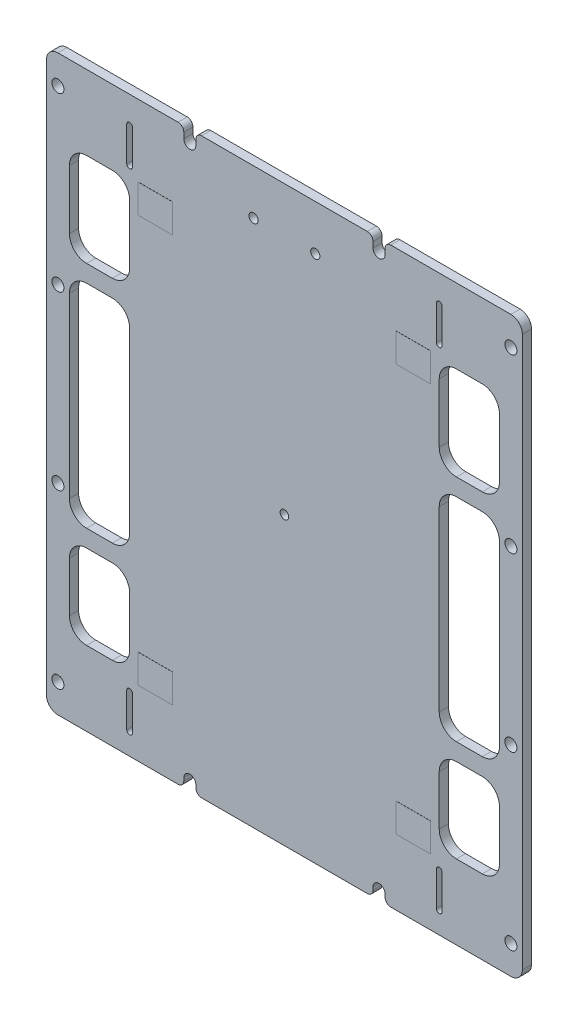
SolidWorks part; units mm, degrees
material "FR4_stuffedProtoboard"
ref_plane "Front Plane" through (0, 0, 0) normal (0, 0, 1) x (1, 0, 0)
ref_plane "Top Plane" through (0, 0, 0) normal (0, 1, 0) x (1, 0, 0)
ref_plane "Right Plane" through (0, 0, 0) normal (1, 0, 0) x (0, 0, -1)
sketch "Sketch1" plane through (0, 0, 0) normal (0, 0, 1) x (1, 0, 0)
  line L1 (-39.5, -50) -> (39.5, -50)
  line L2 (-41.5, -48) -> (-41.5, 48)
  line L3 (-39.5, 50) -> (39.5, 50)
  line L4 (41.5, -48) -> (41.5, 48)
  line L5 (-41.5, -50) -> (41.5, 50) construction
  line L6 (-41.5, 50) -> (41.5, -50) construction
  arc A0 (-39.5, -50) -> (-41.5, -48) centre (-39.5, -48) cw
  arc A1 (39.5, -50) -> (41.5, -48) centre (39.5, -48) ccw
  arc A2 (39.5, 50) -> (41.5, 48) centre (39.5, 48) cw
  arc A3 (-41.5, 48) -> (-39.5, 50) centre (-39.5, 48) cw
  point P0 (0, 0)
  dimension "D3" = 2
  dimension "D1" = 100
  dimension "D2" = 83
extrude "boardOutline" add sketch "Sketch1" along normal blind 1.6
sketch "Sketch2" plane through (0, 0, 1.6) normal (0, 0, 1) x (1, 0, 0)
  line L0 (39.5, 50) -> (-39.5, 50) construction
  line L1 (-41.5, 48) -> (-41.5, -48) construction
  line L2 (-5.385, 42.1) -> (5.385, 42.1) construction
  line L3 (-38, 44.2) -> (-38, 4.2) construction
  line L4 (0, 42.1) -> (0, 50) construction
  circle A0 centre (0, 0) radius 0.75
  circle A1 centre (-38, 44.2) radius 1.05 construction
  circle A2 centre (37.5, 44.2) radius 1.05 construction
  circle A3 centre (37.5, 4.2) radius 1.05 construction
  circle A4 centre (37.5, -35.8) radius 1.05 construction
  circle A5 centre (-38, 4.2) radius 1.05 construction
  circle A6 centre (-38, -35.8) radius 1.05 construction
  circle A7 centre (-5.385, 42.1) radius 0.8
  circle A8 centre (5.385, 42.1) radius 0.8
  dimension "D1" = 1.5
  dimension "D2" = 2.1
  dimension "D9" = 10.77
  dimension "D7" = 1.6
  dimension "D11" = 7.9
  dimension "D3" = 5.8
  dimension "D4" = 3.5
  dimension "D8" = 40
  dimension "D10" = 37.5
  dimension "D5" = 2
  dimension "D6" = 3
extrude "componentHoles" cut sketch "Sketch2" against normal through all
sketch "Sketch4" plane through (0, 0, 1.6) normal (0, 0, 1) x (1, 0, 0)
  line L0 (-27, 39.25) -> (-27, 45.25) construction
  line L1 (-27.5, 39.25) -> (-27.5, 45.25)
  line L2 (-26.5, 39.25) -> (-26.5, 45.25)
  line L3 (39.5, 50) -> (-39.5, 50) construction
  line L4 (-41.5, 48) -> (-41.5, -48) construction
  line L5 (27, 39.25) -> (27, 45.25) construction
  line L6 (26.5, 39.25) -> (26.5, 45.25)
  line L7 (27.5, 39.25) -> (27.5, 45.25)
  line L8 (27, -46.25) -> (27, -40.25) construction
  line L9 (26.5, -46.25) -> (26.5, -40.25)
  line L10 (27.5, -46.25) -> (27.5, -40.25)
  line L11 (-27, -46.25) -> (-27, -40.25) construction
  line L12 (-27.5, -46.25) -> (-27.5, -40.25)
  line L13 (-26.5, -46.25) -> (-26.5, -40.25)
  line L14 (-27, 39.25) -> (27, 39.25) construction
  line L15 (0, 39.25) -> (0, 50) construction
  arc A0 (-27.5, 39.25) -> (-26.5, 39.25) centre (-27, 39.25) ccw
  arc A1 (-26.5, 45.25) -> (-27.5, 45.25) centre (-27, 45.25) ccw
  arc A2 (26.5, 39.25) -> (27.5, 39.25) centre (27, 39.25) ccw
  arc A3 (27.5, 45.25) -> (26.5, 45.25) centre (27, 45.25) ccw
  arc A4 (26.5, -46.25) -> (27.5, -46.25) centre (27, -46.25) ccw
  arc A5 (27.5, -40.25) -> (26.5, -40.25) centre (27, -40.25) ccw
  arc A6 (-27.5, -46.25) -> (-26.5, -46.25) centre (-27, -46.25) ccw
  arc A7 (-26.5, -40.25) -> (-27.5, -40.25) centre (-27, -40.25) ccw
  point P2 (-27, 42.25)
  point P16 (27, 42.25)
  point P23 (27, -43.25)
  point P30 (-27, -43.25)
  dimension "D1" = 4.75
  dimension "D2" = 14
  dimension "D3" = 1
  dimension "D4" = 6
  dimension "D7" = 54
  dimension "D9" = 79.5
  dimension "D5" = 2
  dimension "D6" = 2
extrude "solarCellContactHoles" cut sketch "Sketch4" against normal blind 1.6
sketch "Sketch3" plane through (0, 0, 1.6) normal (0, 0, 1) x (1, 0, 0)
  line L1 (-34.5, 37) -> (-30, 37)
  line L2 (-37.5, 34) -> (-37.5, 23.7)
  line L3 (-34.5, 20.7) -> (-30, 20.7)
  line L4 (-27, 34) -> (-27, 23.7)
  line L5 (-41.5, 48) -> (-41.5, -48) construction
  line L6 (-30, -22.3) -> (-34.5, -22.3)
  line L9 (0, 50) -> (0, -50) construction
  line L10 (39.5, 50) -> (-39.5, 50) construction
  line L11 (-39.5, -50) -> (39.5, -50) construction
  line L12 (-27, -25.3) -> (-27, -34)
  line L13 (-30, -37) -> (-34.5, -37)
  line L14 (-37.5, -25.3) -> (-37.5, -34)
  line L19 (-30, -19.3) -> (-34.5, -19.3)
  line L25 (-27, -16.3) -> (-27, 14.7)
  line L26 (-30, 17.7) -> (-34.5, 17.7)
  line L27 (-37.5, -16.3) -> (-37.5, 14.7)
  arc A0 (-37.5, 23.7) -> (-34.5, 20.7) centre (-34.5, 23.7) ccw
  arc A1 (-30, 20.7) -> (-27, 23.7) centre (-30, 23.7) ccw
  arc A2 (-30, 37) -> (-27, 34) centre (-30, 34) cw
  arc A3 (-34.5, 37) -> (-37.5, 34) centre (-34.5, 34) ccw
  arc A4 (-30, -19.3) -> (-27, -16.3) centre (-30, -16.3) ccw
  arc A5 (-27, -34) -> (-30, -37) centre (-30, -34) cw
  arc A6 (-34.5, -37) -> (-37.5, -34) centre (-34.5, -34) cw
  arc A7 (-34.5, -22.3) -> (-37.5, -25.3) centre (-34.5, -25.3) ccw
  arc A8 (-30, -22.3) -> (-27, -25.3) centre (-30, -25.3) cw
  arc A17 (-34.5, -19.3) -> (-37.5, -16.3) centre (-34.5, -16.3) cw
  arc A18 (-34.5, 17.7) -> (-37.5, 14.7) centre (-34.5, 14.7) ccw
  arc A19 (-27, 14.7) -> (-30, 17.7) centre (-30, 14.7) ccw
  point P12 (-27, 20.7)
  point P15 (-27, 37)
  point P18 (-37.5, 37)
  dimension "D5" = 3
  dimension "D10" = 13
  dimension "D7" = 3
  dimension "D11" = 3
  dimension "D1" = 10.5
  dimension "D2" = 29.3
  dimension "D3" = 13
  dimension "D4" = 4
  dimension "D8" = 3
  dimension "D9" = 3
  dimension "D6" = 37
extrude "windows_1side" cut sketch "Sketch3" against normal through all
sketch "Sketch5" plane through (0, 0, 1.6) normal (0, 0, 1) x (1, 0, 0)
  line L0 (-41.5, 48) -> (-41.5, -48) construction
  line L1 (-25.5, 37.5) -> (-19.5, 37.5)
  line L2 (-25.5, 37.5) -> (-25.5, 32.5)
  line L3 (-25.5, 32.5) -> (-19.5, 32.5)
  line L4 (-19.5, 37.5) -> (-19.5, 32.5)
  line L5 (0, 37.5) -> (0, 50) construction
  line L6 (19.5, 37.5) -> (19.5, 32.5)
  line L7 (25.5, 37.5) -> (25.5, 32.5)
  line L8 (19.5, 32.5) -> (25.5, 32.5)
  line L9 (19.5, 37.5) -> (25.5, 37.5)
  line L10 (19.5, -33.5) -> (19.5, -38.5)
  line L11 (25.5, -33.5) -> (25.5, -38.5)
  line L12 (19.5, -38.5) -> (25.5, -38.5)
  line L13 (19.5, -33.5) -> (25.5, -33.5)
  line L14 (-25.5, -33.5) -> (-25.5, -38.5)
  line L15 (-19.5, -33.5) -> (-19.5, -38.5)
  line L16 (-25.5, -38.5) -> (-19.5, -38.5)
  line L17 (-25.5, -33.5) -> (-19.5, -33.5)
  line L18 (-19.5, 37.5) -> (19.5, 37.5) construction
  line L19 (-25.5, 37.5) -> (-25.5, -33.5) construction
  line L20 (39.5, 50) -> (-39.5, 50) construction
  arc A0 (-27.5, 39.25) -> (-26.5, 39.25) centre (-27, 39.25) ccw construction
  dimension "D1" = 5
  dimension "D2" = 6
  dimension "D3" = 16
  dimension "D4" = 1.75
  dimension "D7" = 45
  dimension "D8" = 71
  dimension "D5" = 2
  dimension "D6" = 2
extrude "contactPads" add sketch "Sketch5" along normal blind 0.02
hole_wizard "M2 Clearance Hole1" positions "Sketch6" profile "Sketch7" hole size "M2" standard "ANSI Metric" end condition through all
sketch "Sketch6" plane through (0, 0, 0) normal (0, 0, -1) x (-1, 0, 0)
  line L5 (39.5, -50) -> (39.5, -45) construction
  line L6 (39.5, -50) -> (-39.5, -50) construction
  line L7 (39.5, -45) -> (39.5, -15) construction
  line L8 (39.5, -15) -> (39.5, 15) construction
  line L9 (39.5, 15) -> (39.5, 45) construction
  line L10 (39.5, 45) -> (39.5, 50) construction
  line L11 (-39.5, 50) -> (39.5, 50) construction
  line L15 (37.5, -27.0602) -> (41.5, -27.0602) construction
  line L16 (37.5, -25.3) -> (37.5, -34) construction
  line L17 (41.5, 48) -> (41.5, -48) construction
  point P0 (39.5, 45)
  point P27 (39.5, -15)
  point P36 (39.5, -45)
  point P38 (39.5, 15)
  point P73 (39.5, -27.0602)
  dimension "D2" = 5
sketch "Sketch7" plane through (-39.5, 45, 0) normal (1, 0, 0) x (0, 1, 0)
  line L0 (0, 0) -> (0, 1.62)
  line L1 (0, 1.62) -> (1.05, 1.62)
  line L2 (1.05, 1.62) -> (1.05, 0)
  line L5 (1.05, 0) -> (0, 0)
  line L11 (0, -6.35) -> (0, 107.95) construction
  dimension "Thru Hole Dia." = 2.1
  dimension "Thru Hole Depth" = 1.62
sketch "Sketch10" plane through (0, 0, 0) normal (0, 0, -1) x (-1, 0, 0)
  line L0 (16.5, 48) -> (16.5, 55.0732) construction
  line L1 (15.45, 48) -> (15.45, 55.0732)
  line L2 (17.55, 48) -> (17.55, 55.0732)
  line L3 (16.5, -48.5) -> (16.5, -55.5732) construction
  line L4 (17.55, -48.5) -> (17.55, -55.5732)
  line L5 (15.45, -48.5) -> (15.45, -55.5732)
  line L6 (41.5, 48) -> (41.5, -48) construction
  line L8 (39.5, -50) -> (-39.5, -50) construction
  line L9 (-39.5, 50) -> (39.5, 50) construction
  arc A0 (15.45, 48) -> (17.55, 48) centre (16.5, 48) ccw
  arc A1 (17.55, 55.0732) -> (15.45, 55.0732) centre (16.5, 55.0732) ccw
  arc A2 (17.55, -48.5) -> (15.45, -48.5) centre (16.5, -48.5) ccw
  arc A3 (15.45, -55.5732) -> (17.55, -55.5732) centre (16.5, -55.5732) ccw
  point P2 (16.5, 51.5366)
  point P7 (16.5, -52.0366)
  dimension "D1" = 1.05
  dimension "D2" = 25
  dimension "D3" = 2
  dimension "D4" = 1.5
extrude "Cut-Extrude1" cut sketch "Sketch10" against normal through all both and the other way through all
fillet "Fillet3" radius 1 4 edges at (-17.55, 50, 0.8) (-15.45, 50, 0.8) (-15.45, -50, 0.8) (-17.55, -50, 0.8)
mirror "Mirror1" about plane through (0, 0, 0) normal (1, 0, 0) of "Cut-Extrude1", "Fillet3", "windows_1side", "M2 Clearance Hole1"
